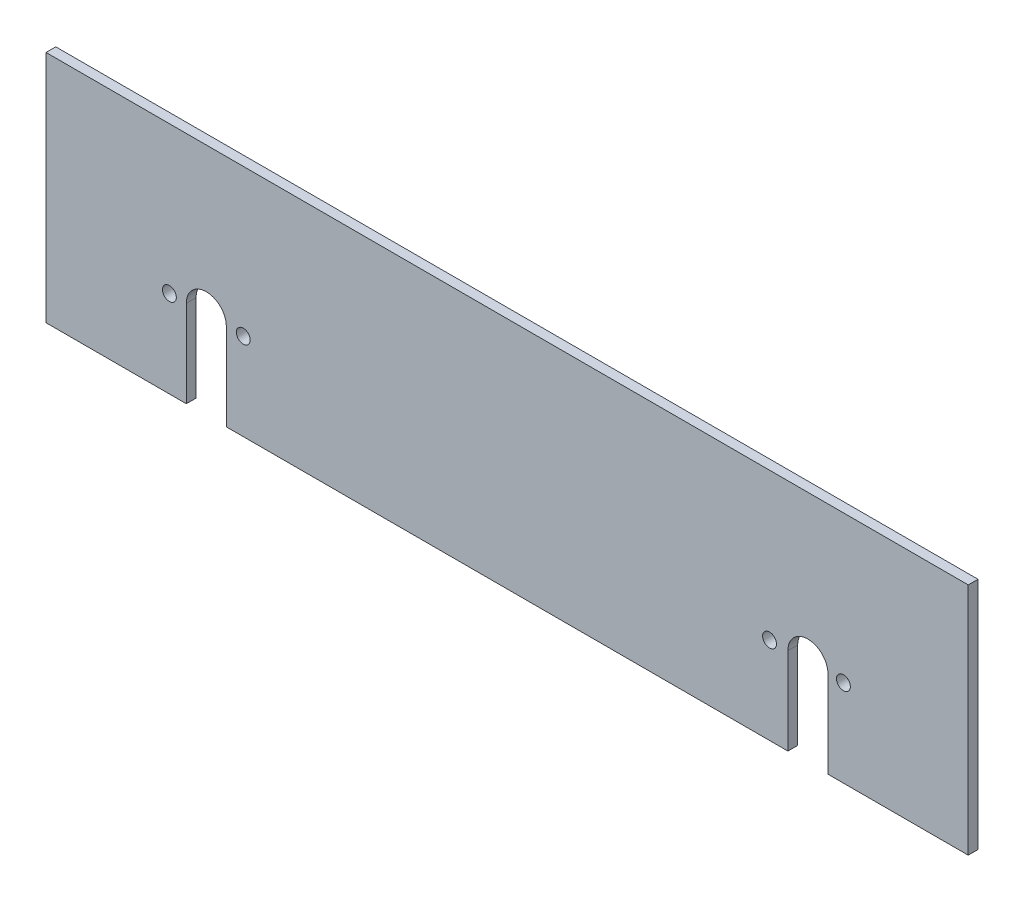
SolidWorks part; units mm, degrees
material "ABS"
ref_plane "X-Y Datum" through (0, 0, 0) normal (0, 0, 1) x (1, 0, 0)
ref_plane "X-Z Datum" through (0, 0, 0) normal (0, 1, 0) x (1, 0, 0)
ref_plane "Y-Z Datum" through (0, 0, 0) normal (1, 0, 0) x (0, 0, -1)
sketch "Sketch1" plane through (0, 0, 0) normal (0, 0, 1) x (1, 0, 0)
  line L1 (-149.85, 38.0375) -> (149.85, 38.0375)
  line L2 (-149.85, 38.0375) -> (-149.85, -38.0375)
  line L3 (-149.85, -38.0375) -> (149.85, -38.0375)
  line L4 (149.85, 38.0375) -> (149.85, -38.0375)
  line L5 (-149.85, 38.0375) -> (149.85, -38.0375) construction
  line L6 (-149.85, -38.0375) -> (149.85, 38.0375) construction
  point P0 (0, 0)
  dimension "D1" = 76.075
  dimension "D2" = 299.7
extrude "Boss-Extrude1" add sketch "Sketch1" along normal blind 3.175
sketch "Sketch3" plane through (0, 0, 0) normal (0, 0, -1) x (-1, 0, 0)
  line L0 (104.25, -9.7625) -> (104.25, -38.0375)
  line L1 (149.85, -38.0375) -> (-149.85, -38.0375) construction
  line L2 (91.25, -9.7625) -> (91.25, -38.0375)
  line L3 (149.85, -38.0375) -> (-149.85, -38.0375)
  line L4 (-104.25, -9.7625) -> (-104.25, -38.0375)
  line L5 (-91.25, -9.7625) -> (-91.25, -38.0375)
  circle A0 centre (97.75, -9.7625) radius 5.75 construction
  circle A1 centre (-97.75, -9.7625) radius 5.75 construction
  circle A2 centre (97.75, -9.7625) radius 5.75 construction
  circle A3 centre (-97.75, -9.7625) radius 5.75 construction
  circle A4 centre (97.75, -9.7625) radius 6.5
  circle A5 centre (-97.75, -9.7625) radius 6.5
  line M2 (-149.85, -38.0375) -> (149.85, -38.0375)
  dimension "D1" = 13
extrude "Cut-Extrude1" cut sketch "Sketch3" against normal through all contours A5 A3 | A3 | A5 L4 L3 L5 | A2 | A4 A2 | A4 L2 L0 M2 region at (97.75, -26.4071, 0) region at (-97.75, -9.7625, 0) region at (-97.75, -26.4071, 0) region at (97.75, -9.7625, 0)
sketch "Sketch4" plane through (0, 0, 0) normal (0, 0, -1) x (-1, 0, 0)
  circle A0 centre (-109.288, -9.7625) radius 2 construction
  circle A1 centre (-85.288, -9.7625) radius 2 construction
  circle A2 centre (85.75, -9.7625) radius 2 construction
  circle A3 centre (109.75, -9.7625) radius 2 construction
  circle A4 centre (-109.288, -9.7625) radius 2 construction
  circle A5 centre (-85.288, -9.7625) radius 2 construction
  circle A6 centre (85.75, -9.7625) radius 2 construction
  circle A7 centre (109.75, -9.7625) radius 2 construction
hole_wizard "M4 Clearance Hole1" positions "Sketch5" profile "Sketch6" hole size "M4" standard "ANSI Metric" end condition through all
sketch "Sketch5" plane through (0, 0, 0) normal (0, 0, -1) x (-1, 0, 0)
  point P0 (-109.288, -9.7625)
  point P3 (-85.288, -9.7625)
  point P6 (85.75, -9.7625)
  point P9 (109.75, -9.7625)
sketch "Sketch6" plane through (109.288, -9.7625, 0) normal (1, 0, 0) x (0, 1, 0)
  line L0 (0, 0) -> (0, 3.175)
  line L1 (0, 3.175) -> (2.25, 3.175)
  line L2 (2.25, 3.175) -> (2.25, 0)
  line L5 (2.25, 0) -> (0, 0)
  line L11 (0, -6.35) -> (0, 107.95) construction
  dimension "Thru Hole Dia." = 4.5
  dimension "Thru Hole Depth" = 3.175
